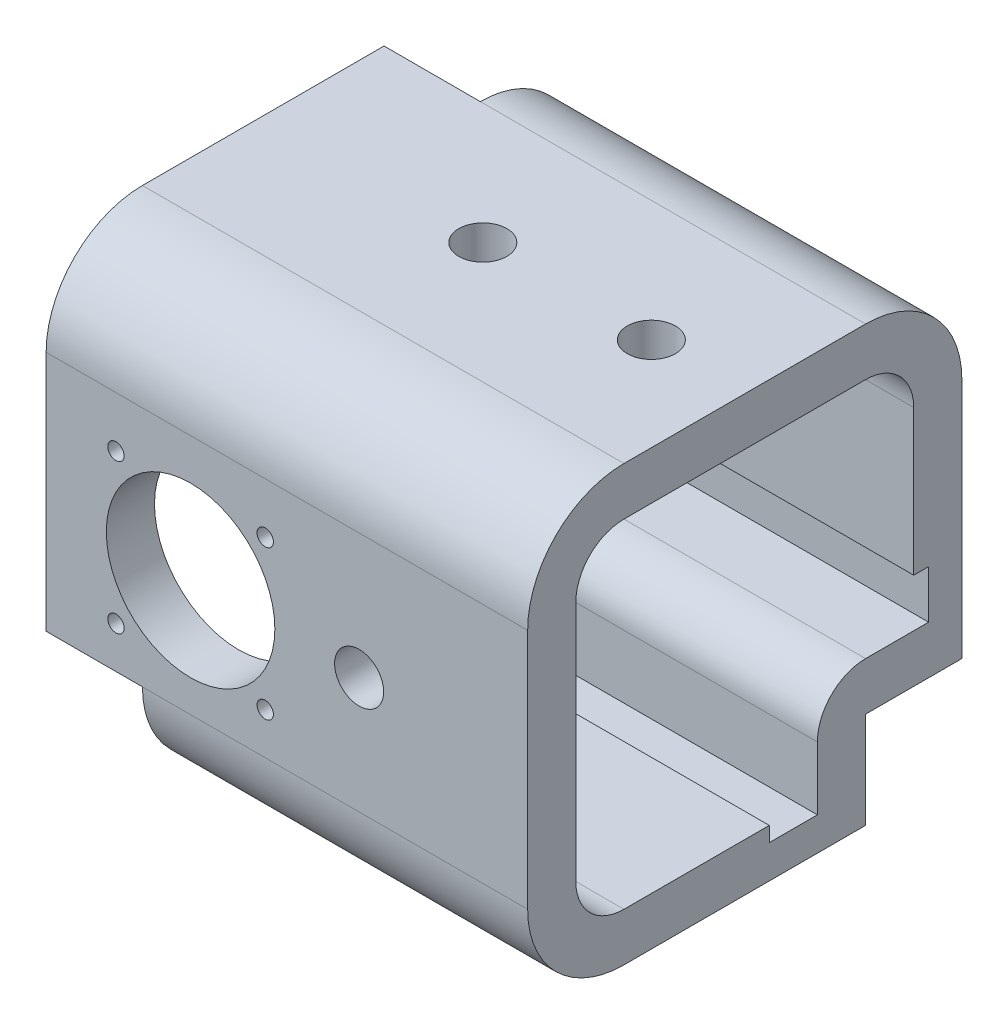
SolidWorks part; units mm, degrees
material "ABS"
ref_plane "Front Plane" through (0, 0, 0) normal (0, 0, 1) x (1, 0, 0)
ref_plane "Top Plane" through (0, 0, 0) normal (0, 1, 0) x (1, 0, 0)
ref_plane "Right Plane" through (0, 0, 0) normal (1, 0, 0) x (0, 0, -1)
sketch "Sketch2" plane through (0, 0, 0) normal (1, 0, 0) x (0, 0, -1)
  line L0 (-40.8, -13.55) -> (-40.8, -17.45) construction
  line L1 (19.375, 36.025) -> (-30.8, 36.025)
  line L2 (29.375, 26.025) -> (29.375, -24.15)
  line L3 (19.375, -34.15) -> (-30.8, -34.15)
  line L4 (-40.8, 26.025) -> (-40.8, -24.15)
  line L5 (-50.8, 15) -> (-40.8, 15) construction
  line L10 (-48.05, 15) -> (-59.05, 15) construction
  line L11 (-50.8, -15) -> (-40.8, -15) construction
  line L12 (-59.05, -15) -> (-48.05, -15) construction
  line L13 (19.375, 46.025) -> (-30.8, 46.025)
  line L14 (-50.8, 26.025) -> (-50.8, -24.15)
  line L15 (19.375, -44.15) -> (-30.8, -44.15)
  line L16 (39.375, 26.025) -> (39.375, -24.15)
  line L19 (-40.05, -21.15) -> (-29.05, -21.15) construction
  arc A0 (-30.8, 36.025) -> (-40.8, 26.025) centre (-30.8, 26.025) ccw
  arc A1 (-30.8, -34.15) -> (-40.8, -24.15) centre (-30.8, -24.15) cw
  arc A2 (19.375, -34.15) -> (29.375, -24.15) centre (19.375, -24.15) ccw
  arc A3 (19.375, 36.025) -> (29.375, 26.025) centre (19.375, 26.025) cw
  arc A4 (-30.8, 46.025) -> (-50.8, 26.025) centre (-30.8, 26.025) ccw
  arc A5 (-30.8, -44.15) -> (-50.8, -24.15) centre (-30.8, -24.15) cw
  arc A6 (19.375, -44.15) -> (39.375, -24.15) centre (19.375, -24.15) ccw
  arc A7 (19.375, 46.025) -> (39.375, 26.025) centre (19.375, 26.025) cw
  arc A8 (19.375, 36.025) -> (29.375, 26.025) centre (19.375, 26.025) cw construction
  dimension "D1" = 10
  dimension "D2" = 10
  dimension "D3" = 3
  dimension "D4" = 70.175
extrude "Boss-Extrude1" add sketch "Sketch2" along normal blind 70 and the other way blind 30
sketch "Sketch3" plane through (0, 0, 50.8) normal (0, 0, 1) x (1, 0, 0)
  arc A0 (-14.0466, 5.2624) -> (-13.6647, 6.1867) centre (0, 0) ccw construction
  arc A1 (-14.0466, 5.2624) -> (-13.6647, 6.1867) centre (0, 0) ccw construction
  circle A2 centre (15.5, -15.5) radius 1.7 construction
  circle A3 centre (15.5, 15.5) radius 1.7 construction
  circle A4 centre (-15.5, 15.5) radius 1.7 construction
  circle A5 centre (-15.5, -15.5) radius 1.7 construction
  circle A6 centre (15.5, -15.5) radius 1.7
  circle A7 centre (15.5, 15.5) radius 1.7
  circle A8 centre (-15.5, 15.5) radius 1.7
  circle A9 centre (-15.5, -15.5) radius 1.7
  circle A10 centre (0, 0) radius 17.5
  arc A11 (-16.3877, 6.1395) -> (-15.9422, 7.2178) centre (0, 0) ccw construction
  circle A12 centre (35, 0) radius 5.1 construction
  circle A13 centre (35, 0) radius 5.1
  dimension "D1" = 2.5
extrude "Cut-Extrude1" cut sketch "Sketch3" against normal up to next
sketch "Sketch4" plane through (0, 46.025, 0) normal (0, 1, 0) x (1, 0, 0)
  line L0 (50.6, -5.7125) -> (15.6, -5.7125) construction
  line L1 (-30, 19.375) -> (70, 19.375) construction
  line L2 (-30, -30.8) -> (70, -30.8) construction
  line L3 (28.05, -18.8125) -> (38.15, -18.8125) construction
  line L4 (28.05, -18.8125) -> (38.15, -18.8125) construction
  line L5 (33.1, -18.8125) -> (33.1, -5.7125) construction
  circle A0 centre (15.6, -5.7125) radius 5
  circle A1 centre (50.6, -5.7125) radius 5
  point P12 (33.1, -5.7125)
  dimension "D1" = 10
  dimension "D2" = 35
extrude "Cut-Extrude2" cut sketch "Sketch4" against normal up to next
sketch "Sketch5" plane through (0, 0, 50.8) normal (0, 0, 1) x (1, 0, 0)
  line L0 (-30, -24.15) -> (70, -24.15) construction
  line L1 (-10, -24.15) -> (-30, -24.15)
  line L2 (-10, -24.15) -> (-10, -44.15)
  line L3 (-10, -44.15) -> (-30, -44.15)
  line L4 (-30, -24.15) -> (-30, -44.15)
  line L5 (-30, 26.025) -> (-30, -24.15) construction
  line L6 (-30, -44.15) -> (70, -44.15) construction
  dimension "D1" = 20
extrude "Cut-Extrude3" cut sketch "Sketch5" against normal through all both and the other way through all
sketch "Sketch6" plane through (0, 46.025, 0) normal (0, 1, 0) x (1, 0, 0)
  line L0 (-30, 19.375) -> (-30, -30.8) construction
  line L1 (-30, 39.375) -> (-10, 39.375)
  line L2 (-30, 39.375) -> (-30, 19.375)
  line L3 (-30, 19.375) -> (-10, 19.375)
  line L4 (-10, 39.375) -> (-10, 19.375)
  line L5 (-30, 19.375) -> (70, 19.375) construction
  line L6 (-30, 39.375) -> (70, 39.375) construction
  dimension "D1" = 20
extrude "Cut-Extrude4" cut sketch "Sketch6" against normal through all
sketch "Sketch7" plane through (-10, 0, 0) normal (-1, 0, 0) x (0, 0, 1)
  line L10 (-19.375, -44.15) -> (30.8, -44.15) construction
  line L11 (-39.375, -24.15) -> (-19.375, -24.15)
  line L12 (-39.375, -24.15) -> (-39.375, -44.15)
  line L13 (-39.375, -44.15) -> (-19.375, -44.15)
  line L14 (-19.375, -24.15) -> (-19.375, -44.15)
  line L15 (-39.375, -24.15) -> (-39.375, 26.025) construction
  line L16 (-29.375, 26.025) -> (-29.375, -24.15) construction
  line L17 (-29.375, -4.15) -> (-32.475, -4.15)
  line L18 (-29.375, -4.15) -> (-29.375, -24.15)
  line L19 (-29.375, -24.15) -> (-32.475, -24.15)
  line L20 (-32.475, -4.15) -> (-32.475, -24.15)
  line L21 (-19.375, -34.15) -> (30.8, -34.15) construction
  line L22 (-19.375, -37.25) -> (0.625, -37.25)
  line L23 (-19.375, -37.25) -> (-19.375, -34.15)
  line L24 (-19.375, -34.15) -> (0.625, -34.15)
  line L25 (0.625, -37.25) -> (0.625, -34.15)
  line L26 (-32.475, -24.7292) -> (-32.475, -25.6692) construction
  arc M8 (-19.375, -34.15) -> (-29.375, -24.15) centre (-19.375, -24.15) cw
  arc M14 (-39.375, -24.15) -> (-19.375, -44.15) centre (-19.375, -24.15) ccw
  dimension "D1" = 20
  dimension "D2" = 20
extrude "Cut-Extrude5" cut sketch "Sketch7" against normal through all contours L14 L11 M8 M14 | L18 L17 L20 L19 | L23 L22 L25 L24 region at (-10, -34.053, -29.278)
sketch "Sketch8" plane through (-10, 0, 0) normal (-1, 0, 0) x (0, 0, 1)
  line L0 (-39.375, -14.1507) -> (-19.3742, -14.1507)
  line L1 (-39.375, -24.15) -> (-39.375, 26.025) construction
  line L2 (-9.3742, -24.1507) -> (-9.3742, -44.15)
  line L3 (-19.375, -44.15) -> (30.8, -44.15) construction
  line L4 (-39.375, -24.1507) -> (-19.3742, -24.1507)
  line L5 (-19.3742, -24.1507) -> (-19.3742, -44.15)
  line L6 (-20.8742, -24.1507) -> (-25.4942, -24.1507) construction
  line L7 (-19.3742, -25.6507) -> (-19.3742, -30.2707) construction
  line L8 (-39.375, -14.1507) -> (-39.375, -24.1507)
  line L9 (-19.3742, -44.15) -> (-9.3742, -44.15)
  line L10 (-9.3742, -14.1507) -> (-9.3742, -44.15) construction
  line L11 (-39.375, -14.1507) -> (-9.3742, -14.1507) construction
  arc A0 (-9.3742, -24.1507) -> (-19.3742, -14.1507) centre (-19.3742, -24.1507) ccw
  dimension "D2" = 10
  dimension "D1" = 10
extrude "Boss-Extrude2" add sketch "Sketch8" against normal up to surface (80 mm away) up to face at (70, -3.0793, 1.6957)
